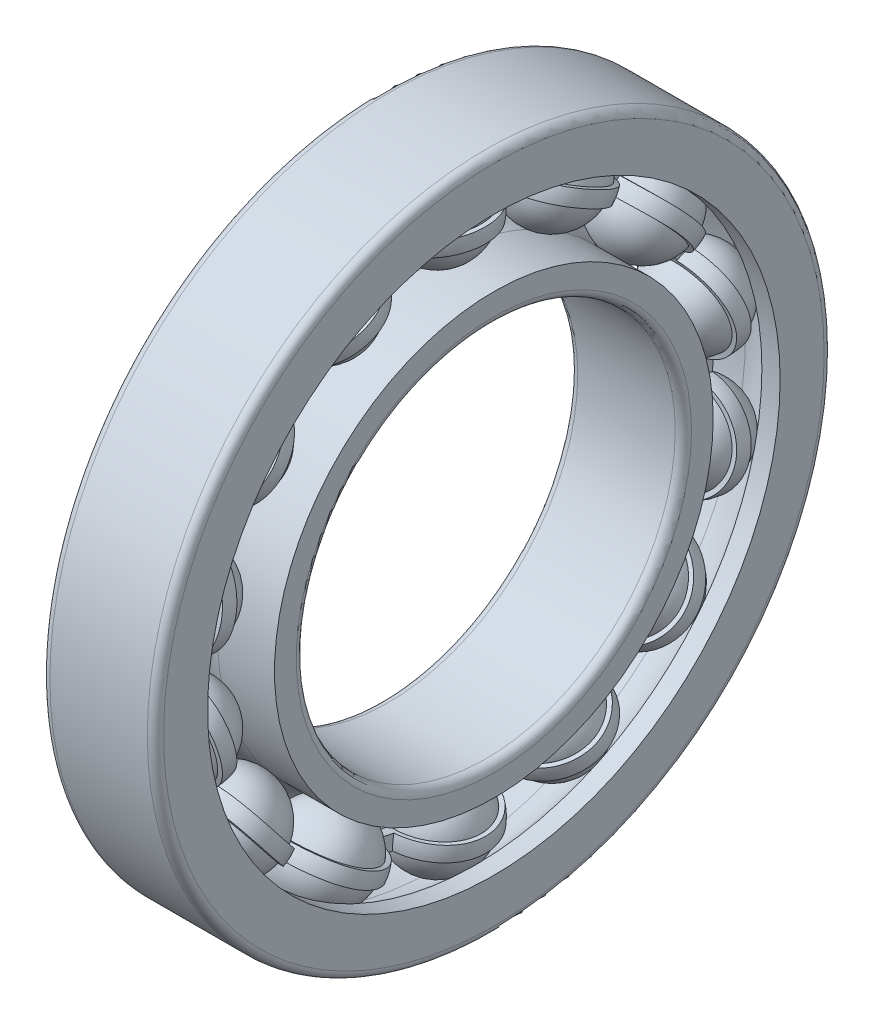
SolidWorks part; units mm, degrees
ref_plane "Plane1" through (0, 0, 0) normal (0, 0, 1) x (1, 0, 0)
ref_plane "Plane2" through (0, 0, 0) normal (0, 1, 0) x (1, 0, 0)
ref_plane "Plane3" through (0, 0, 0) normal (1, 0, 0) x (0, 0, -1)
sketch "Clipboard" plane through (0, 0, 0) normal (0, 0, 1) x (1, 0, 0)
  line L0 (-10, 0) -> (10, 0) construction
  line L1 (0, 0) -> (21.6965, -5.4095)
  line L2 (0, 0) -> (94.6038, 23.5874)
  line L3 (0, 0) -> (21.6965, -5.4095)
  line L4 (0, 0) -> (-22.3471, -0.7804)
  dimension "BallCLRad" = 97.5
sketch "CagSpiSke" plane through (0, 0, 0) normal (0, 0, 1) x (1, 0, 0)
  line L0 (1.65, 94.75) -> (1.65, 100.25)
  line L1 (1.65, 100.25) -> (-1.65, 100.25)
  line L2 (-1.65, 100.25) -> (-1.65, 94.75)
  line L3 (-1.65, 94.75) -> (1.65, 94.75)
  line L4 (-20.6375, 0) -> (20.6375, 0) construction
  line L5 (0, 0) -> (0, 23.7692) construction
  dimension "OD" = 200.5
  dimension "ID" = 189.5
revolve "CageSpine" add sketch "CagSpiSke" angle 360 about L4 reverse direction yes
ref_axis "Axis1" through (-50, 0, 0) along (1, 0, 0)
sketch "CagBalSke" plane through (0, 0, 0) normal (0, 0, 1) x (1, 0, 0)
  line L0 (-18.15, 97.5) -> (18.15, 97.5)
  line L1 (-1.905, 97.5) -> (1.905, 97.5) construction
  line L2 (-10, 0) -> (10, 0) construction
  line L3 (0, 0) -> (0, 24) construction
  arc A0 (18.15, 97.5) -> (-18.15, 97.5) centre (0, 97.5) cw
  dimension "BallCLRad" = 97.5
revolve "CageBall" add sketch "CagBalSke" angle 360 about L1 reverse direction yes
pattern_circular "CageBalls" count 14 every 25.714 about axis through (-50, 0, 0) along (1, 0, 0) of "CageBall"
sketch "CagTrmODSke" plane through (0, 0, 0) normal (0, 0, 1) x (1, 0, 0)
  line L0 (18.151, 100.25) -> (18.151, 115.651)
  line L1 (18.151, 115.651) -> (-18.151, 115.651)
  line L2 (-18.151, 115.651) -> (-18.151, 100.25)
  line L3 (-18.151, 100.25) -> (18.151, 100.25)
  line L4 (-20.6375, 0) -> (20.6375, 0) construction
  line L5 (0, 0) -> (0, 25) construction
  dimension "Width" = 36.302
  dimension "ID" = 200.5
  dimension "OD" = 231.302
revolve "CageTrimOD" cut sketch "CagTrmODSke" angle 360 about L4 reverse direction yes
sketch "CagTrmIDSke" plane through (0, 0, 0) normal (0, 0, 1) x (1, 0, 0)
  line L0 (18.151, 79.351) -> (18.151, 94.75)
  line L1 (18.151, 94.75) -> (-18.151, 94.75)
  line L2 (-18.151, 94.75) -> (-18.151, 79.351)
  line L3 (-18.151, 79.351) -> (18.151, 79.351)
  line L4 (-20.6375, 0) -> (20.6375, 0) construction
  line L5 (0, 0) -> (0, 25) construction
  dimension "Width" = 36.302
  dimension "ID" = 158.702
  dimension "OD" = 189.5
revolve "CageTrimID" cut sketch "CagTrmIDSke" angle 360 about L4
sketch "BalSimSke" plane through (0, 0, 0) normal (0, 0, 1) x (1, 0, 0)
  line L0 (-10, 0) -> (10, 0) construction
  line L1 (-10, 97.5) -> (10, 97.5) construction
  line L2 (0, 0) -> (0, 23) construction
  circle A0 centre (0, 97.5) radius 16.5
  dimension "BallCLRad" = 97.5
  dimension "Ball_diameter" = 33
revolve "BallsSimplified" [suppressed] add sketch "BalSimSke" angle 360 about L0
sketch "BalDetSke" plane through (0, 0, 0) normal (0, 0, 1) x (1, 0, 0)
  line L0 (-16.5, 97.5) -> (16.5, 97.5)
  line L1 (-1.905, 97.5) -> (1.905, 97.5) construction
  line L2 (0, 0) -> (0, 25) construction
  arc A0 (16.5, 97.5) -> (-16.5, 97.5) centre (0, 97.5) cw
  dimension "BallCLRad" = 97.5
  dimension "Ball_diameter" = 33
revolve "BallDetailed" add sketch "BalDetSke" angle 360 about L1
sketch "InnRacSke" plane through (0, 0, 0) normal (0, 0, 1) x (1, 0, 0)
  line L0 (-14.2605, 89.25) -> (-21, 89.25)
  line L1 (-21, 89.25) -> (-21, 73)
  line L2 (-18, 70) -> (18, 70)
  line L3 (21, 73) -> (21, 81.025)
  line L4 (0, 81.025) -> (21, 81.025)
  line L5 (-20.6375, 0) -> (20.6375, 0) construction
  line L6 (0, 0) -> (0, 30) construction
  arc A0 (-21, 73) -> (-18, 70) centre (-18, 73) ccw
  arc A1 (18, 70) -> (21, 73) centre (18, 73) ccw
  arc A2 (0, 81.025) -> (-14.2605, 89.25) centre (0, 97.5) cw
  dimension "BallCLRad" = 97.5
  dimension "Fillet_radius" = 3
  dimension "Ball_diameter" = 32.95
  dimension "ID" = 140
  dimension "OD" = 178.5
  dimension "Width" = 42
revolve "InnerRace" add sketch "InnRacSke" angle 360 about L5
sketch "OutRacSke" plane through (0, 0, 0) normal (0, 0, 1) x (1, 0, 0)
  line L0 (0, 113.975) -> (-21, 113.975)
  line L1 (-21, 113.975) -> (-21, 122)
  line L2 (-18, 125) -> (18, 125)
  line L3 (21, 122) -> (21, 105.75)
  line L4 (21, 105.75) -> (14.2605, 105.75)
  line L5 (-20.6375, 0) -> (20.6375, 0) construction
  line L6 (0, 0) -> (0, 30) construction
  arc A0 (-21, 122) -> (-18, 125) centre (-18, 122) cw
  arc A1 (18, 125) -> (21, 122) centre (18, 122) cw
  arc A2 (14.2605, 105.75) -> (0, 113.975) centre (0, 97.5) ccw
  dimension "BallCLRad" = 97.5
  dimension "Fillet_radius" = 3
  dimension "Ball_diameter" = 32.95
  dimension "Width" = 42
revolve "OuterRace" add sketch "OutRacSke" angle 360 about L5
pattern_circular "BallsDetailed" count 14 every 25.714 about axis through (-50, 0, 0) along (1, 0, 0) of "BallDetailed"
equation "\"BallCLRad@Clipboard\" = ( \"OD@OutRacSke\" + \"ID@InnRacSke\" ) / 4"
equation "\"BallCLRad@BalSimSke\" = \"BallCLRad@Clipboard\""
equation "\"BallCLRad@BalDetSke\" = \"BallCLRad@Clipboard\""
equation "\"BallCLRad@InnRacSke\" = \"BallCLRad@Clipboard\""
equation "\"BallCLRad@OutRacSke\" = \"BallCLRad@Clipboard\""
equation "\"Ball_diameter@InnRacSke\" = \"Ball_diameter@BalDetSke\" - 0.05"
equation "\"Ball_diameter@OutRacSke\" = \"Ball_diameter@BalDetSke\" - 0.05"
equation "\"Ball_diameter@BalSimSke\" = \"Ball_diameter@BalDetSke\""
equation "\"Width@OutRacSke\" = \"Width@InnRacSke\""
equation "\"Fillet_radius@OutRacSke\" = \"Fillet_radius@InnRacSke\""
equation "\"Max_count@Clipboard\" = int( 3.14159265 / atn(( \"Ball_diameter@BalDetSke\" / 2) / sqr( \"BallCLRad@Clipboard\"  *  \"BallCLRad@Clipboard\" - ( \"Ball_diameter@BalDetSke\" / 2) *  ( \"Ball_diameter@BalDetSke\" / 2))))"
equation "\"Max_count@Clipboard\" = ((sgn( \"Max_count@Clipboard\" - \"Count@Clipboard\" )-1)*( \"Max_count@Clipboard\" - \"Count@Clipboard\" ))/-2+ \"Count@Clipboard\""
equation "\"Count@BallsDetailed\" = int( \"Show_count@Clipboard\" ) "
equation "\"Count@BallsDetailed\" = ((sgn( \"Count@BallsDetailed\" - \"Max_count@Clipboard\" )-1)*( \"Count@BallsDetailed\" - \"Max_count@Clipboard\" ))/-2+ \"Max_count@Clipboard\""
equation "\"Count@BallsDetailed\" = ((sgn( \"Count@BallsDetailed\" - \"Min_count@Clipboard\" )+1)*( \"Count@BallsDetailed\" - \"Min_count@Clipboard\"))/2 +\"Min_count@Clipboard\""
equation "\"Angle@BallsDetailed\" = 360.0 / \"Max_count@Clipboard\""
equation "\"BallCLRad@CagBalSke\" = \"BallCLRad@Clipboard\""
equation "\"Count@CageBalls\" = \"Count@BallsDetailed\""
equation "\"Angle@CageBalls\" = \"Angle@BallsDetailed\""
equation "\"Angle@CageSpine\" =  \"Angle@CageBalls\" * ( \"Count@CageBalls\" -1 + int( \"Count@CageBalls\" / \"Max_count@Clipboard\" ) )  + 0.001 -  int( \"Count@CageBalls\" / \"Max_count@Clipboard\" ) * 0.001"
equation "\"Angle@CageSpine\" =  \"Angle@CageSpine\" * int( \"Min_count@Clipboard\" / 2) + int(1 / \"Min_count@Clipboard\")  * 0.001"
equation "\"CageWallOD@CagBalSke\" =  \"Ball_diameter@BalDetSke\" * 1.1"
equation "\"Thickness@CagSpiSke\" =  \"Ball_diameter@BalDetSke\" * 0.1"
equation "\"OD@CagTrmODSke\" = \"BallCLRad@Clipboard\" * 2 + \"CageWallOD@CagBalSke\" + 0.002"
equation "\"ID@CagTrmODSke\" = \"BallCLRad@Clipboard\" * 2 + \"Ball_diameter@BalDetSke\" / 6"
equation "\"OD@CagTrmIDSke\" = \"BallCLRad@Clipboard\" * 2 - \"Ball_diameter@BalDetSke\" / 6"
equation "\"ID@CagTrmIDSke\" = \"BallCLRad@Clipboard\" * 2 - \"CageWallOD@CagBalSke\" + 0.002"
equation "\"OD@CagSpiSke\" = \"ID@CagTrmODSke\""
equation "\"ID@CagSpiSke\" = \"OD@CagTrmIDSke\""
equation "\"Width@CagTrmODSke\" = \"CageWallOD@CagBalSke\" + 0.002"
equation "\"Width@CagTrmIDSke\" = \"CageWallOD@CagBalSke\" + 0.002"
